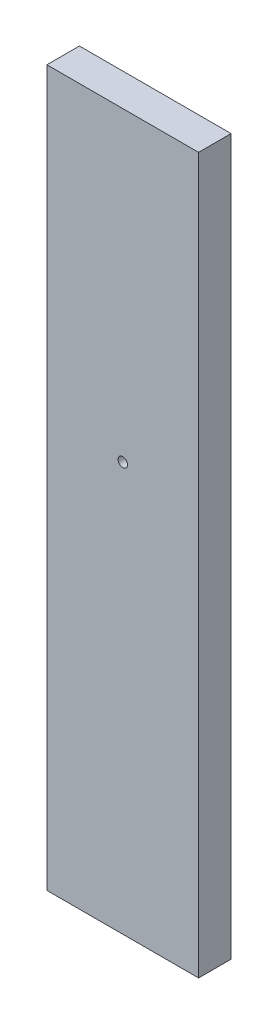
SolidWorks part; units mm, degrees
ref_plane "Front Plane" through (0, 0, 0) normal (0, 0, 1) x (1, 0, 0)
ref_plane "Top Plane" through (0, 0, 0) normal (0, 1, 0) x (1, 0, 0)
ref_plane "Right Plane" through (0, 0, 0) normal (1, 0, 0) x (0, 0, -1)
sketch "Sketch1" plane through (0, 0, 0) normal (0, 1, 0) x (1, 0, 0)
  line L1 (0, 0) -> (88.9, 0)
  line L2 (0, 0) -> (0, 19.05)
  line L3 (0, 19.05) -> (88.9, 19.05)
  line L4 (88.9, 0) -> (88.9, 19.05)
  dimension "D1" = 19.05
  dimension "D2" = 88.9
extrude "Boss-Extrude1" add sketch "Sketch1" along normal blind 419.1
sketch "Sketch2" plane through (0, 0, 0) normal (0, 0, 1) x (1, 0, 0)
  line L0 (44.45, 419.1) -> (44.45, 239.6416) construction
  line L1 (0, 419.1) -> (88.9, 419.1) construction
  circle A0 centre (44.45, 239.6416) radius 2.7781
  dimension "D1" = 5.5562
  dimension "D2" = 179.4584
extrude "Cut-Extrude1" cut sketch "Sketch2" against normal through all
